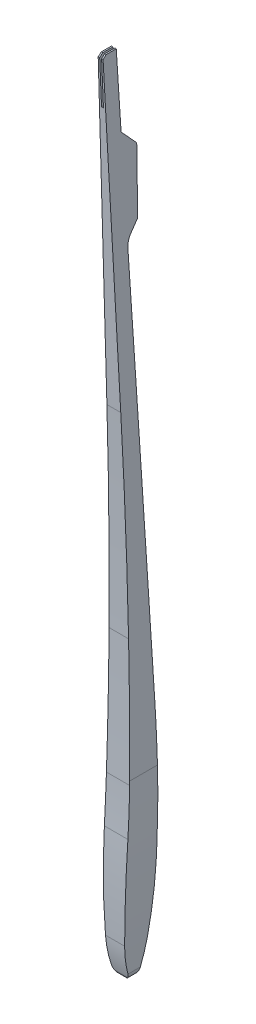
SolidWorks part; units mm, degrees
ref_plane "Front Plane" through (0, 0, 0) normal (0, 0, 1) x (1, 0, 0)
ref_plane "Top Plane" through (0, 0, 0) normal (0, 1, 0) x (1, 0, 0)
ref_plane "Right Plane" through (0, 0, 0) normal (1, 0, 0) x (0, 0, -1)
sketch "Sketch1" plane through (0, 0, 0) normal (1, 0, 0) x (0, 0, -1)
  line L0 (-78.5961, 496.4175) -> (37.2278, 496.4175) construction
  line L1 (-9.525, 304.8) -> (28.575, 304.8) construction
  line L2 (0, 304.8) -> (0, 0) construction
  line L3 (1.0213, 1065.6718) -> (10.694, 1079.103)
  line L4 (-27.1607, 65.9105) -> (17.6308, 65.9105) construction
  line L5 (11.8763, 1082.7678) -> (11.8763, 1187.7195)
  line L6 (11.8763, 1187.7195) -> (-13.5361, 1215.2864)
  line L7 (-13.5361, 1215.2864) -> (-19.8238, 1336.7381)
  line L8 (-19.8238, 1336.7381) -> (-36.6687, 1336.7381)
  line L9 (-36.6687, 1336.7381) -> (-41.6113, 1332.1818)
  line L10 (-19.8238, 820.1016) -> (-41.6113, 1332.1818)
  arc A0 (-7.6557, 5.3976) -> (7.6557, 5.3976) centre (0, 8.128) ccw
  arc A1 (7.6557, 5.3976) -> (20.0794, 52.6423) centre (-261.9388, 101.5472) ccw
  arc A2 (20.0794, 52.6423) -> (31.2926, 156.5086) centre (-782.6283, 191.8401) ccw
  arc A3 (31.2926, 156.5086) -> (31.8418, 170.4411) centre (-1716.2031, 232.3657) ccw
  arc A4 (31.8418, 170.4411) -> (30.1448, 385.5899) centre (-2451.9942, 258.4311) ccw
  arc A5 (30.1448, 385.5899) -> (-4.7668, 1045.9034) centre (-201637.2133, -9945.7343) ccw
  arc A6 (-4.7668, 1045.9034) -> (1.0213, 1065.6718) centre (26.1322, 1047.5878) cw
  arc A7 (10.694, 1079.103) -> (11.8763, 1082.7678) centre (5.6052, 1082.7678) ccw
  arc A8 (-7.6557, 5.3976) -> (-17.7894, 57.8201) centre (158.8151, 64.7686) cw
  arc A9 (-17.7894, 57.8201) -> (-16.0363, 211.5245) centre (1496.7221, 117.4084) cw
  arc A10 (-16.0363, 211.5245) -> (-12.9269, 287.0724) centre (-1813.0084, 323.323) ccw
  arc A11 (-12.9269, 287.0724) -> (-11.6095, 494.6337) centre (-7538.1927, 438.6183) ccw
  arc A12 (-11.6095, 494.6337) -> (-19.8238, 820.1016) centre (-9161.9195, 426.534) ccw
  point P13 (0, 0)
  dimension "D4" = 8.128
  dimension "D1" = 304.8
  dimension "D2" = 38.1
  dimension "D3" = 28.575
extrude "Boss-Extrude1" add sketch "Sketch1" along normal blind 31.75 and the other way blind 31.75
ref_plane "Plane1" through (0, 0, -33.3998) normal (0, 0, -1) x (-1, 0, 0)
sketch "Sketch2" plane through (0, 0, -33.3998) normal (0, 0, 1) x (1, 0, 0)
  line L0 (-78.9139, 1964.5454) -> (836.4194, 1964.5454) construction
  line L1 (19.05, 293.1843) -> (3.9688, 1336.7381)
  line L2 (0, 0) -> (0, 1336.7381) construction
  line L3 (31.75, 1336.7381) -> (-31.75, 1336.7381) construction
  line L4 (-31.75, 0) -> (31.75, 0) construction
  line L5 (-3.9688, 1336.7381) -> (0, 1336.7381) construction
  line L6 (-19.05, 293.1843) -> (-3.9688, 1336.7381)
  line L7 (3.9688, 1336.7381) -> (0, 1336.7381) construction
  line L8 (0, 0) -> (31.75, 0)
  line L9 (-31.75, 1336.7381) -> (31.75, 1336.7381) construction
  line L10 (31.75, 0) -> (31.75, 1336.7381)
  line L11 (31.75, 1336.7381) -> (3.9688, 1336.7381)
  line L12 (-3.9688, 1336.7381) -> (-31.75, 1336.7381)
  line L13 (-31.75, 1336.7381) -> (-31.75, 0)
  line L14 (-31.75, 0) -> (0, 0)
  arc A0 (13.6981, 12.9953) -> (-13.6981, 12.9953) centre (0, 13.7172) cw
  arc A1 (-13.6981, 12.9953) -> (-19.05, 293.1843) centre (4157.8315, 232.8208) cw
  arc A2 (13.6981, 12.9953) -> (19.05, 293.1843) centre (-4157.8315, 232.8208) ccw
  point P16 (0, 0)
  dimension "D1" = 13.7172
  dimension "D2" = 3.9688
  dimension "D3" = 38.1
extrude "Cut-Extrude2" cut sketch "Sketch2" along normal through all contours A0 A2 L1 L11 L10 L8 | A1 A0 L14 L13 L12 L6 region at (-21.7075, 757.5963, -33.3998) region at (21.7075, 757.5963, -33.3998)
sketch "Sketch3" plane through (0, 2.5497, -49.2489) normal (0, 0.0517, -0.9987) x (-1, 0, 0)
  line L0 (3.9688, 1336.8462) -> (-3.9688, 1336.8462) construction
  line L1 (-1.5875, 1336.8462) -> (1.5875, 1336.8462)
  line L2 (-1.5875, 1336.8462) -> (-1.5875, 1260.6462)
  line L3 (-1.5875, 1260.6462) -> (1.5875, 1260.6462)
  line L4 (1.5875, 1336.8462) -> (1.5875, 1260.6462)
  line L5 (1.5875, 1336.8462) -> (3.9688, 1336.8462) construction
  line L6 (-1.5875, 1336.8462) -> (-3.9688, 1336.8462) construction
  dimension "D1" = 76.2
  dimension "D2" = 3.175
extrude "Cut-Extrude3" cut sketch "Sketch3" against normal through all
